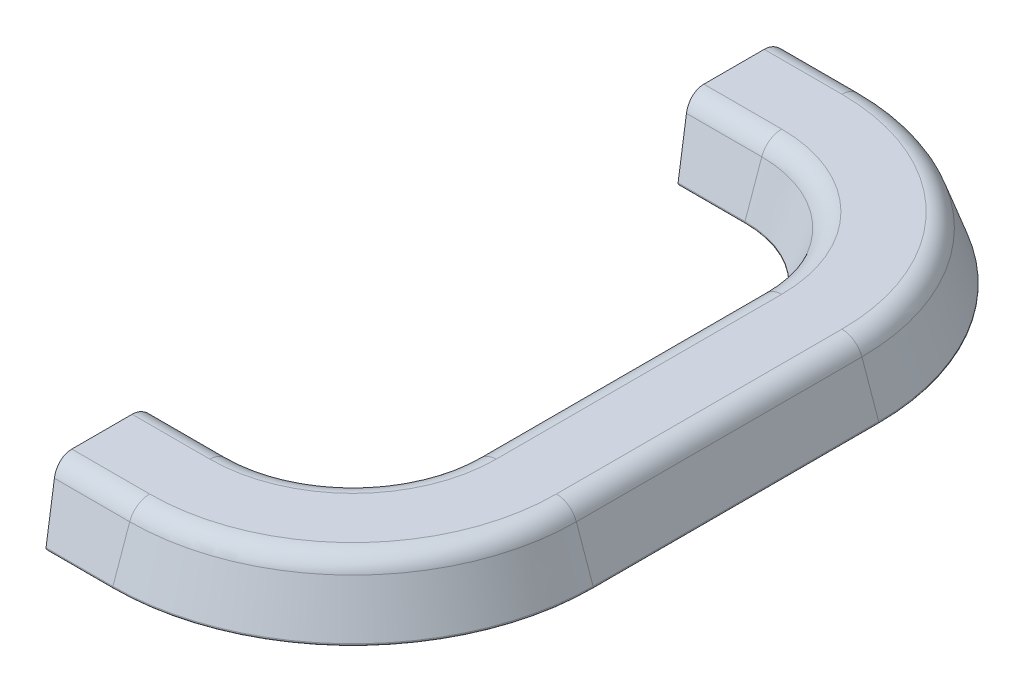
SolidWorks part; units mm, degrees
note: '?' marks a value the reader was unsure of.
ref_plane "Front Plane" through (0, 0, 0) normal (0, 0, 1) x (1, 0, 0)
ref_plane "Top Plane" through (0, 0, 0) normal (0, 1, 0) x (1, 0, 0)
ref_plane "Right Plane" through (0, 0, 0) normal (1, 0, 0) x (0, 0, -1)
sketch "Sketch1" plane through (0, 0, 0) normal (1, 0, 0) x (0, 0, -1)
  line L0 (-75.9772, 0) -> (-75.9772, 15.3502) construction
  line L1 (-92.2304, 0) -> (-59.724, 0)
  line L2 (-92.2304, 0) -> (-86.8199, 15.3502)
  line L3 (-86.8199, 15.3502) -> (-65.1345, 15.3502)
  line L4 (-59.724, 0) -> (-65.1345, 15.3502)
sketch "Sketch2" plane through (0, 0, 0) normal (0, 1, 0) x (1, 0, 0)
  line L0 (0, -59.724) -> (18.7014, -59.724)
  line L1 (44.1014, -34.324) -> (44.1014, 34.324)
  line L2 (18.7014, 59.724) -> (0, 59.724)
  line L3 (0, 0) -> (44.1014, 0) construction
  arc A0 (18.7014, -59.724) -> (44.1014, -34.324) centre (18.7014, -34.324) ccw
  arc A1 (44.1014, 34.324) -> (18.7014, 59.724) centre (18.7014, 34.324) ccw
  dimension "D1" = 25.4
sweep "Sweep1" add profiles "Sketch1" path "Sketch2"
ref_axis "Axis1" through (0, 0, 50) along (0, 0, -1)?
ref_plane "Plane1" through (2.625, 0.4629, 0) normal (-0.9848, -0.1736, 0) x (0, 0, 1)
other "SurfaceCut1"
fillet "Fillet1" radius 5.08 10 edges at (9.3507, 15.3502, -65.1345) (40.4877, 15.3502, -56.1103) (49.5119, 15.3502, 0) (40.4877, 15.3502, 56.1103) (9.3507, 15.3502, -86.8199) (55.8216, 15.3502, -71.4442) (71.1973, 15.3502, 0) (55.8216, 15.3502, 71.4442) (9.3507, 15.3502, 65.1345) (9.3507, 15.3502, 86.8199)
shell "Shell1" thickness 2.54
sketch "Sketch4" plane through (2.625, 0.4629, 0) normal (-0.9848, -0.1736, 0) x (0, 0, 1)
  line L1 (-75.9772, 15.117) -> (-75.9772, 8.7828) construction
  line L2 (-68.7303, 15.117) -> (-83.2241, 15.117) construction
  line L3 (-78.9482, 12.5378) -> (-78.5996, 8.5533)
  line L4 (-68.7303, 12.5378) -> (-83.2241, 12.5378) construction
  line L5 (-73.0062, 12.5378) -> (-73.3548, 8.5533)
  line L7 (-78.9482, 12.5378) -> (-73.0062, 12.5378)
  arc A0 (-78.5996, 8.5533) -> (-73.3548, 8.5533) centre (-75.9772, 8.7828) ccw
  dimension "D1" = 2.6324
  dimension "D2" = 8.9667
  dimension "D3" = 10
extrude "Extrude1" add sketch "Sketch4" against normal up to next
hole_wizard "7/64 (0.10938) Diameter Hole1" positions "Sketch6" profile "Sketch5" hole size "7/64" standard "Ansi Inch"
sketch "Sketch6" plane through (2.625, 0.4629, 0) normal (-0.9848, -0.1736, 0) x (0, 0, 1)
  point P0 (-75.9772, 8.7828)
sketch "Sketch5" plane through (1.0999, 9.1122, -75.9772) normal (0, 0, 1) x (0.1736, -0.9848, 0)
  line L0 (0, 0) -> (0, 13.5347)
  line L1 (0, 13.5347) -> (1.3891, 12.7)
  line L2 (1.3891, 12.7) -> (1.3891, 0)
  line L5 (1.3891, 0) -> (0, 0)
  line L10 (0, 13.5347) -> (-1.3891, 12.7) construction
  line L11 (0, -6.35) -> (0, 107.95) construction
  dimension "Hole Dia." = 2.7783
  dimension "Hole Depth" = 12.7
  dimension "Drill Angle" = 118
mirror "Mirror1" about plane through (0, 0, 0) normal (0, 0, 1) of "Extrude1", "7/64 (0.10938) Diameter Hole1"
fillet "Fillet2" radius 0.3969 16 edges at (11.9208, 12.8102, -73.1805) (37.232, 12.8102, -75.9772) (11.9208, 12.8102, -78.7739) (10.704, 0, 59.724) (36.6619, 0, 52.2845) (44.1014, 0, 0) (36.6619, 0, -52.2845) (10.704, 0, 92.2304) (59.6474, 0, 75.27) (76.6078, 0, 0) (59.6474, 0, -75.27) (10.704, 0, -59.724) (10.704, 0, -92.2304) (11.9208, 12.8102, 78.7739) (37.232, 12.8102, 75.9772) (11.9208, 12.8102, 73.1805)
